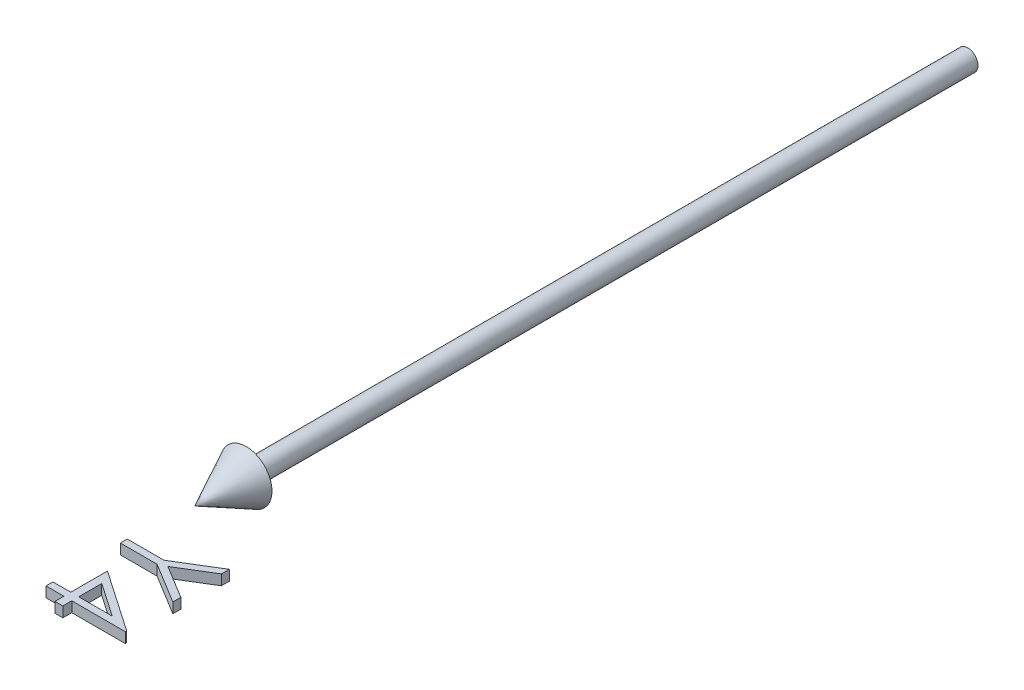
SolidWorks part; units mm, degrees
ref_plane "Front Plane" through (0, 0, 0) normal (0, 0, 1) x (1, 0, 0)
ref_plane "Top Plane" through (0, 0, 0) normal (0, 1, 0) x (1, 0, 0)
ref_plane "Right Plane" through (0, 0, 0) normal (1, 0, 0) x (0, 0, -1)
sketch "Sketch2" plane through (0, 0, 0) normal (0, 1, 0) x (1, 0, 0)
  line L0 (0, 41.95) -> (0, -114.4521) construction
  line L1 (-36.8894, 0) -> (41.4965, 0) construction
  line L2 (0, -150) -> (5, -140)
  line L3 (5, -140) -> (2, -140)
  line L4 (2, -140) -> (2, 0)
  line L5 (2, 0) -> (0, 0)
  line L6 (0, 0) -> (0, -150)
  dimension "D1" = 150
  dimension "D2" = 2
  dimension "D3" = 10
  dimension "D4" = 5
revolve "Revolve1" add sketch "Sketch2" angle 360 about L0
sketch "Sketch3" plane through (0, 0, 0) normal (0, 1, 0) x (1, 0, 0)
  line L0 (0, -157.5) -> (0, -253.3976) construction
  line L1 (-33.6232, 0) -> (34.179, 0) construction
  text T0 "Y4\r\n\r\n" font "Century Gothic" height 15
  dimension "D1" = 157.5
extrude "Boss-Extrude1" add sketch "Sketch3" against normal blind 1 and the other way blind 1 separate body
equation "\"D1@Sketch2\"=\"frame_arrow_length\""
equation "\"D2@Sketch2\"=\"frame_arrow_odA\"/2"
equation "\"D4@Sketch2\"=\"frame_arrow_head_od\""
equation "\"D3@Sketch2\"=\"frame_arrow_head_length\""
equation "\"frame_arrow_length\"=150"
equation "\"frame_arrow_head_length\"=10"
equation "\"frame_arrow_head_od\"=5"
equation "\"frame_arrow_odA\"=4"
equation "\"D1@Sketch3\"=\"frame_arrow_length\"*1.05"
